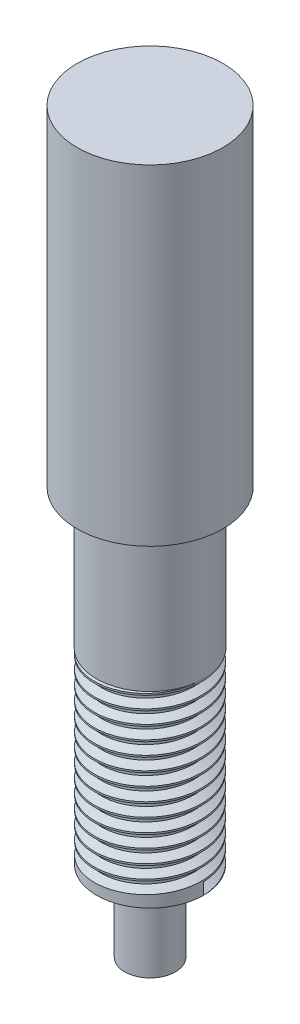
SolidWorks part; units mm, degrees
material "AISI 316 Annealed Stainless Steel Bar (SS)"
ref_plane "Front Plane" through (0, 0, 0) normal (0, 0, 1) x (1, 0, 0)
ref_plane "Top Plane" through (0, 0, 0) normal (0, 1, 0) x (1, 0, 0)
ref_plane "Right Plane" through (0, 0, 0) normal (1, 0, 0) x (0, 0, -1)
sketch "Sketch2" plane through (0, 0, 0) normal (0, 0, 1) x (1, 0, 0)
  line L0 (0, 0) -> (0, 508.8276) construction
  line L1 (0, 0) -> (6, 0)
  line L2 (0, 0) -> (0, 19.05)
  line L3 (0, 19.05) -> (6, 19.05)
  line L4 (6, 0) -> (6, 19.05)
  line L5 (0, 19.05) -> (12.6746, 19.05)
  line L6 (0, 19.05) -> (0, 63.5)
  line L7 (0, 63.5) -> (12.6746, 63.5)
  line L8 (12.6746, 19.05) -> (12.6746, 63.5)
  line L9 (0, 63.5) -> (12.721, 63.5)
  line L10 (0, 63.5) -> (0, 96.52)
  line L11 (0, 96.52) -> (12.721, 96.52)
  line L12 (12.721, 63.5) -> (12.721, 96.52)
  line L13 (0, 96.52) -> (17.272, 96.52)
  line L14 (0, 96.52) -> (0, 174.752)
  line L15 (0, 174.752) -> (17.272, 174.752)
  line L16 (17.272, 96.52) -> (17.272, 174.752)
  dimension "D1" = 78.232
  dimension "D2" = 17.272
  dimension "D4" = 33.02
  dimension "D3" = 12.721
  dimension "D5" = 44.45
  dimension "D6" = 12.6746
  dimension "D7" = 19.05
  dimension "D8" = 6
revolve "Revolve1" add sketch "Sketch2" angle 360 about L0 region at (3, 9.525, 0) region at (6.3373, 41.275, 0) region at (6.3605, 80.01, 0) region at (8.636, 135.636, 0)
thread "Thread1" pitch 3.175 method cut profile "Thread Profile2" start angle 0, offset 0, length 0, pitch 3.175, diameter 25.3492
ref_plane "Plane2" through (12.6746, 19.05, 0) normal (0, 0, 1) x (1, 0, 0)
sketch "Thread Profile2" plane through (12.6746, 19.05, 0) normal (0, 0, 1) x (1, 0, 0)
  line L0 (0, 0) -> (0, 3.175) construction
  line L11 (0, 0) -> (0, 2.7781)
  line L12 (0, 2.7781) -> (-1.7185, 1.7859)
  line L13 (-1.7185, 1.7859) -> (-1.7185, 0.9922)
  line L15 (-1.7185, 0.9922) -> (0, 0)
  line L17 (-1.7185, 1.3891) -> (0, 1.3891) construction
  point P2 (0, 0)
  dimension "Pitch" = 3.175
  dimension "Profile_Angle" = 60
  dimension "Profile_Land" = 0.7937
  dimension "Profile_Height" = 1.7185
equation "\"hole diamiter\"= 1.36in"
equation "\"wheel depth\"= 2.88"
equation "\"press_tolerance\"= 0.00165"
equation "\"wheel_connection\"= \"hole diamiter\"'https://at-machining.com/tolerance-press-fit/"
equation "\"D1@Sketch2\"=\"wheel depth\"+0.2"
equation "\"D2@Sketch2\"=\"wheel_connection\"/2"
equation "\"fitting depth\"= 1.3"
equation "\"D4@Sketch2\"=\"fitting depth\""
equation "\"bearing_id\"= 1"
equation "\"bearing_connection\"= \"bearing_id\" + \"press_tolerance\"'https://at-machining.com/tolerance-press-fit/"
equation "\"D3@Sketch2\"=\"bearing_connection\"/2"
equation "\"thread length\"= 1.75"
equation "\"major_diamiter\"= 0.9980'https://www.machiningdoctor.com/threadinfo/?tid=109"
equation "\"D5@Sketch2\"=\"thread length\""
equation "\"D6@Sketch2\"=\"major_diamiter\"/2"
equation "\"coupling diamiter\"= 12mm"
equation "\"coupling lenght\"= 1.5 / 2"
equation "\"D7@Sketch2\"=\"coupling lenght\""
equation "\"D8@Sketch2\"=\"coupling diamiter\"/2"
